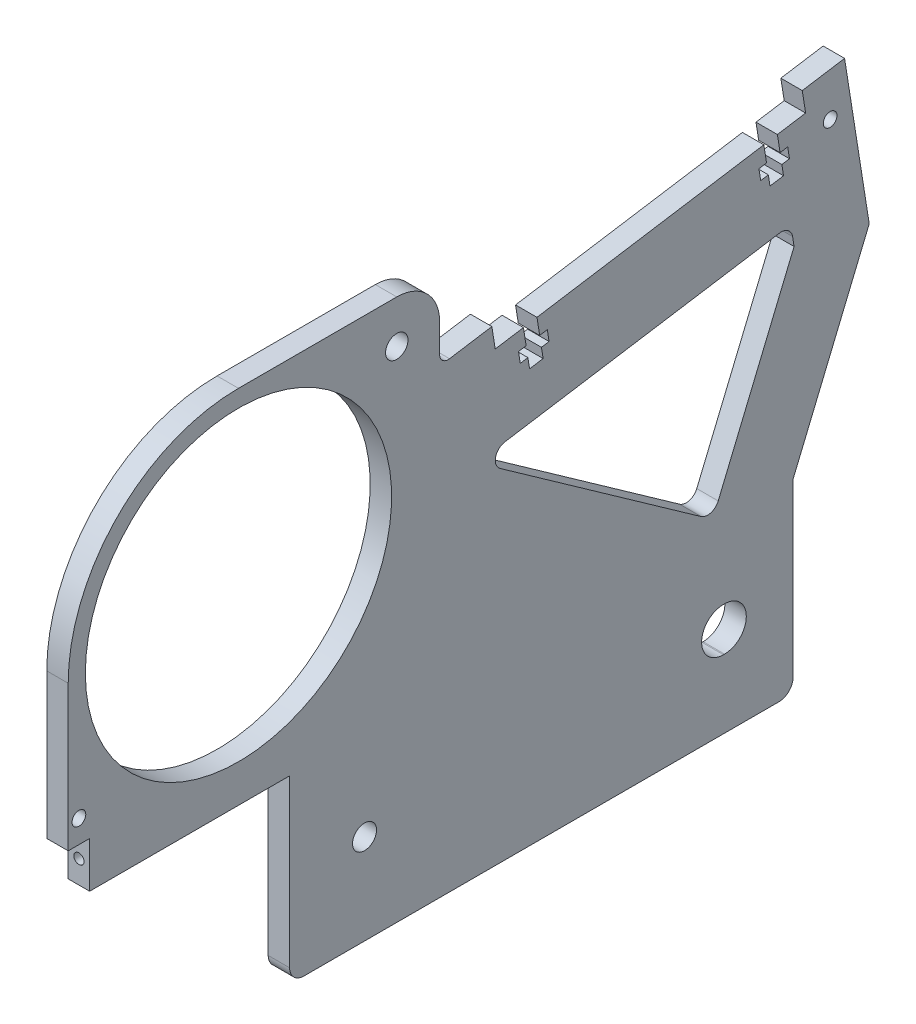
SolidWorks part; units mm, degrees
ref_plane "Front Plane" through (0, 0, 0) normal (0, 0, 1) x (1, 0, 0)
ref_plane "Top Plane" through (0, 0, 0) normal (0, 1, 0) x (1, 0, 0)
ref_plane "Right Plane" through (0, 0, 0) normal (1, 0, 0) x (0, 0, -1)
sketch "Sketch1" plane through (0, 0, 0) normal (1, 0, 0) x (0, 0, -1)
  line L0 (-28.1703, 0) -> (77.3828, 0)
  line L1 (80.5578, 3.175) -> (80.5578, 38.5047)
  line L2 (-80.5578, 82.55) -> (-80.5578, 50.292)
  line L3 (-7.5328, 120.4) -> (-42.7078, 120.4) construction
  line L4 (-75.7953, 50.292) -> (-75.7953, 40.132)
  line L5 (65.3178, 20.066) -> (65.0638, 20.066) construction
  line L6 (65.3178, 15.2273) -> (65.0638, 15.2273)
  line L7 (-75.7953, 40.132) -> (-31.3453, 40.132)
  line L8 (-7.5328, 120.4) -> (-42.7078, 120.4)
  line L9 (80.5578, 38.5047) -> (80.5578, 41.307)
  line L10 (-31.3453, 40.132) -> (-31.3453, 3.175)
  line L11 (-80.5578, 50.292) -> (-75.7953, 50.292)
  line L12 (65.3178, 24.9047) -> (65.0638, 24.9047)
  line L15 (77.5375, 90.1504) -> (16.5054, 80.4839) construction
  line L16 (15.4361, 75.9014) -> (60.0992, 44.3133) construction
  line L17 (63.9111, 45.4115) -> (80.7745, 85.9497) construction
  line L18 (80.7745, 85.9497) -> (80.4436, 88.0391) construction
  line L19 (77.5375, 90.1504) -> (16.5054, 80.4839)
  line L20 (15.4361, 75.9014) -> (60.0992, 44.3133)
  line L21 (63.9111, 45.4115) -> (80.7745, 85.9497)
  line L22 (80.7745, 85.9497) -> (80.4436, 88.0391)
  line L25 (80.5578, 41.307) -> (97.4765, 81.978) construction
  line L26 (97.4765, 81.978) -> (92.0007, 116.5505) construction
  line L27 (92.0007, 116.5505) -> (82.593, 115.0605) construction
  line L28 (82.593, 115.0605) -> (83.338, 110.3566) construction
  line L29 (83.338, 110.3566) -> (77.0662, 109.3632) construction
  line L30 (80.5578, 41.307) -> (97.4765, 81.978)
  line L31 (97.4765, 81.978) -> (92.0007, 116.5505)
  line L32 (92.0007, 116.5505) -> (82.593, 115.0605)
  line L33 (82.593, 115.0605) -> (83.338, 110.3566)
  line L34 (83.338, 110.3566) -> (77.0662, 109.3632)
  line L35 (77.0662, 109.3632) -> (77.6672, 105.5688) construction
  line L36 (74.6567, 105.092) -> (74.0557, 108.8864) construction
  line L37 (72.9633, 104.8238) -> (74.6567, 105.092) construction
  line L38 (77.6672, 105.5688) -> (79.3605, 105.837) construction
  line L39 (79.3605, 105.837) -> (79.7529, 103.3596) construction
  line L40 (79.7529, 103.3596) -> (78.0595, 103.0914) construction
  line L41 (73.3557, 102.3464) -> (72.9633, 104.8238) construction
  line L42 (75.0491, 102.6146) -> (73.3557, 102.3464) construction
  line L43 (75.4216, 100.2627) -> (75.0491, 102.6146) construction
  line L44 (78.432, 100.7395) -> (75.4216, 100.2627) construction
  line L45 (78.0595, 103.0914) -> (78.432, 100.7395) construction
  line L46 (74.0557, 108.8864) -> (23.6303, 100.8998) construction
  line L47 (77.0662, 109.3632) -> (77.6672, 105.5688)
  line L48 (74.6567, 105.092) -> (74.0557, 108.8864)
  line L49 (72.9633, 104.8238) -> (74.6567, 105.092)
  line L50 (77.6672, 105.5688) -> (79.3605, 105.837)
  line L51 (79.3605, 105.837) -> (79.7529, 103.3596)
  line L52 (79.7529, 103.3596) -> (78.0595, 103.0914)
  line L53 (73.3557, 102.3464) -> (72.9633, 104.8238)
  line L54 (75.0491, 102.6146) -> (73.3557, 102.3464)
  line L55 (75.4216, 100.2627) -> (75.0491, 102.6146)
  line L56 (78.432, 100.7395) -> (75.4216, 100.2627)
  line L57 (78.0595, 103.0914) -> (78.432, 100.7395)
  line L58 (74.0557, 108.8864) -> (23.6303, 100.8998)
  line L59 (23.6303, 100.8998) -> (24.2312, 97.1054) construction
  line L60 (24.2312, 97.1054) -> (25.9246, 97.3736) construction
  line L61 (25.9246, 97.3736) -> (26.317, 94.8962) construction
  line L62 (26.317, 94.8962) -> (24.6236, 94.628) construction
  line L63 (24.6236, 94.628) -> (24.9961, 92.2761) construction
  line L64 (24.9961, 92.2761) -> (21.9857, 91.7993) construction
  line L65 (21.9857, 91.7993) -> (21.6131, 94.1512) construction
  line L66 (21.6131, 94.1512) -> (19.9198, 93.883) construction
  line L67 (19.9198, 93.883) -> (19.5274, 96.3604) construction
  line L68 (19.5274, 96.3604) -> (21.2208, 96.6286) construction
  line L69 (21.2208, 96.6286) -> (20.6198, 100.423) construction
  line L70 (20.6198, 100.423) -> (14.348, 99.4297) construction
  line L71 (23.6303, 100.8998) -> (24.2312, 97.1054)
  line L72 (24.2312, 97.1054) -> (25.9246, 97.3736)
  line L73 (25.9246, 97.3736) -> (26.317, 94.8962)
  line L74 (26.317, 94.8962) -> (24.6236, 94.628)
  line L75 (24.6236, 94.628) -> (24.9961, 92.2761)
  line L76 (24.9961, 92.2761) -> (21.9857, 91.7993)
  line L77 (21.9857, 91.7993) -> (21.6131, 94.1512)
  line L78 (21.6131, 94.1512) -> (19.9198, 93.883)
  line L79 (19.9198, 93.883) -> (19.5274, 96.3604)
  line L80 (19.5274, 96.3604) -> (21.2208, 96.6286)
  line L81 (21.2208, 96.6286) -> (20.6198, 100.423)
  line L82 (20.6198, 100.423) -> (14.348, 99.4297)
  line L83 (14.348, 99.4297) -> (13.6029, 104.1335) construction
  line L84 (13.6029, 104.1335) -> (4.1952, 102.6435) construction
  line L85 (1.9922, 104.525) -> (1.9922, 110.875) construction
  line L86 (14.348, 99.4297) -> (13.6029, 104.1335)
  line L87 (13.6029, 104.1335) -> (4.1952, 102.6435)
  line L88 (1.9922, 104.525) -> (1.9922, 110.875)
  arc A0 (65.3178, 15.2273) -> (65.3178, 24.9047) centre (65.3178, 20.066) ccw
  circle A1 centre (-42.7078, 82.55) radius 31.5 construction
  circle A2 centre (65.3178, 20.066) radius 77.47 construction
  circle A3 centre (-78.1765, 55.372) radius 1.524
  arc A4 (65.0638, 24.9047) -> (65.0638, 15.2273) centre (65.0638, 20.066) ccw
  arc A5 (-42.7078, 120.4) -> (-80.5578, 82.55) centre (-42.7078, 82.55) ccw
  arc A6 (-28.1703, 0) -> (-31.3453, 3.175) centre (-28.1703, 3.175) cw
  arc A7 (77.3828, 0) -> (80.5578, 3.175) centre (77.3828, 3.175) ccw
  arc A10 (16.5054, 80.4839) -> (15.4361, 75.9014) centre (16.9028, 77.9752) ccw construction
  circle A11 centre (-14.6922, 20.066) radius 2.667
  arc A12 (60.0992, 44.3133) -> (63.9111, 45.4115) centre (61.5659, 46.387) ccw construction
  arc A14 (80.4436, 88.0391) -> (77.5375, 90.1504) centre (77.9349, 87.6417) ccw construction
  arc A15 (16.5054, 80.4839) -> (15.4361, 75.9014) centre (16.9028, 77.9752) ccw
  circle A16 centre (-42.7078, 82.55) radius 34.04
  arc A17 (60.0992, 44.3133) -> (63.9111, 45.4115) centre (61.5659, 46.387) ccw
  arc A19 (80.4436, 88.0391) -> (77.5375, 90.1504) centre (77.9349, 87.6417) ccw
  circle A23 centre (88.7869, 106.3978) radius 1.524 construction
  circle A25 centre (88.7869, 106.3978) radius 1.524
  arc A26 (1.9922, 104.525) -> (4.1952, 102.6435) centre (3.8972, 104.525) ccw construction
  arc A27 (1.9922, 110.875) -> (-7.5328, 120.4) centre (-7.5328, 110.875) ccw construction
  circle A28 centre (-7.5328, 110.875) radius 2.4892 construction
  arc A29 (1.9922, 104.525) -> (4.1952, 102.6435) centre (3.8972, 104.525) ccw
  arc A30 (1.9922, 110.875) -> (-7.5328, 120.4) centre (-7.5328, 110.875) ccw
  circle A31 centre (-7.5328, 110.875) radius 2.4892
  point P13 (65.1908, 20.066)
  dimension "D4" = 9.6774
  dimension "D7" = 4.7625
  dimension "D8" = 63
  dimension "D12" = 3.175
  dimension "D14" = 2.54
  dimension "D15" = 154.94
  dimension "D18" = 5.334
  dimension "D19" = 5.08
  dimension "D17" = 3.048
  dimension "D2" = 40.132
  dimension "D3" = 20.066
  dimension "D5" = 15.24
  dimension "D6" = 44.45
  dimension "D10" = 161.1156
  dimension "D11" = 95.25
  dimension "D21" = 0.254
  dimension "D22" = 10.16
  dimension "D16" = 2.3813
extrude "Boss-Extrude1" add sketch "Sketch1" along normal blind 4.7625
sketch "Sketch2" plane through (0, 0, 75.7953) normal (0, 0, 1) x (1, 0, 0)
  line L0 (0, 50.292) -> (0, 40.132) construction
  line L1 (4.7625, 40.132) -> (0, 40.132) construction
  circle A0 centre (2.3813, 45.212) radius 1.1303
  point P4 (0, 45.212)
  point P7 (2.3813, 40.132)
  dimension "D1" = 2.2606
extrude "Cut-Extrude1" cut sketch "Sketch2" against normal blind 6.35
